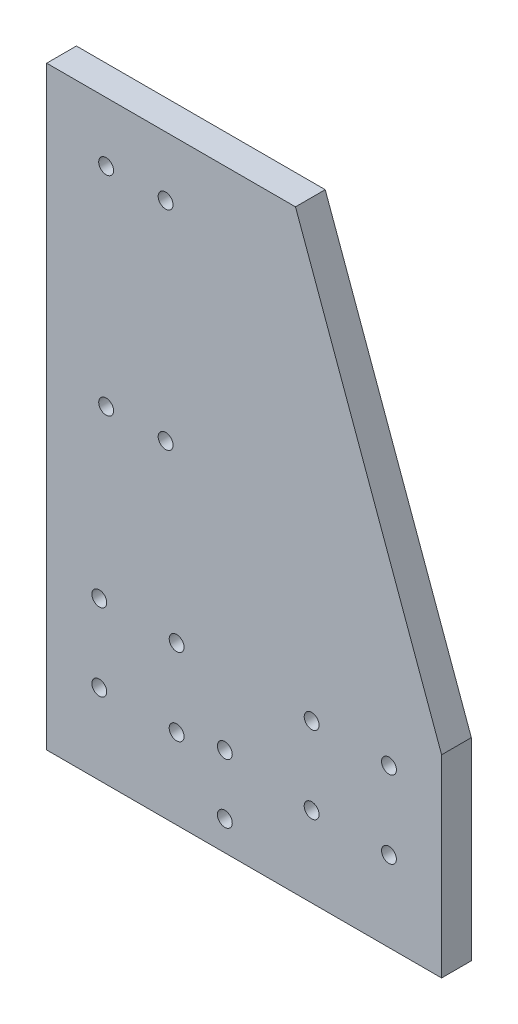
SolidWorks part; units mm, degrees
ref_plane "Front Plane" through (0, 0, 0) normal (0, 0, 1) x (1, 0, 0)
ref_plane "Top Plane" through (0, 0, 0) normal (0, 1, 0) x (1, 0, 0)
ref_plane "Right Plane" through (0, 0, 0) normal (1, 0, 0) x (0, 0, -1)
sketch "Sketch1" plane through (0, 0, 0) normal (0, 0, 1) x (1, 0, 0)
  line L0 (66.4, -5.8678) -> (66.4, 56.1407) construction
  line L5 (0, 0) -> (132.8, 0)
  line L6 (0, 0) -> (0, 200)
  line L7 (0, 200) -> (83.664, 200)
  line L8 (132.8, 0) -> (132.8, 65)
  line L9 (71.4, 57.9012) -> (71.4, -9.8319) construction
  line L23 (102.1, 57.9012) -> (102.1, -7.5742) construction
  line L24 (83.9369, 40) -> (119.8285, 40) construction
  line L25 (52.3456, 19.92) -> (67.8875, 19.92) construction
  line L26 (64.535, 29.92) -> (62.2225, 33.9254)
  line L27 (62.2225, 33.9254) -> (57.5975, 33.9254)
  line L28 (57.5975, 33.9254) -> (55.285, 29.92)
  line L29 (55.285, 29.92) -> (57.5975, 25.9146)
  line L30 (57.5975, 25.9146) -> (62.2225, 25.9146)
  line L31 (62.2225, 25.9146) -> (64.535, 29.92)
  line L32 (62.2225, 13.9254) -> (64.535, 9.92)
  line L33 (57.5975, 13.9254) -> (62.2225, 13.9254)
  line L34 (55.285, 9.92) -> (57.5975, 13.9254)
  line L35 (57.5975, 5.9146) -> (55.285, 9.92)
  line L36 (62.2225, 5.9146) -> (57.5975, 5.9146)
  line L37 (64.535, 9.92) -> (62.2225, 5.9146)
  line L38 (132.8, 65) -> (83.664, 200)
  circle A12 centre (115.1, 27) radius 2.5
  circle A13 centre (89.1, 27) radius 2.5
  circle A14 centre (115.1, 53) radius 2.5
  circle A15 centre (89.1, 53) radius 2.5
  circle A16 centre (17.7, 53) radius 2.5
  circle A17 centre (17.7, 27) radius 2.5
  circle A18 centre (43.7, 27) radius 2.5
  circle A19 centre (43.7, 53) radius 2.5
  circle A20 centre (59.91, 29.92) radius 4.0054 construction
  circle A21 centre (59.91, 29.92) radius 2.5
  circle A23 centre (59.91, 9.92) radius 2.5
  dimension "D4" = 5
  dimension "D13" = 5
  dimension "D1" = 200
  dimension "D2" = 132.8
  dimension "D3" = 26
  dimension "D5" = 61.4
  dimension "D6" = 30.7
  dimension "D7" = 27
  dimension "D8" = 13
  dimension "D9" = 29.92
  dimension "D10" = 10
  dimension "D11" = 9.25
  dimension "D12" = 11.49
  dimension "D14" = 65
  dimension "D15" = 20
  dimension "D16" = 9.92
extrude "Boss-Extrude1" add sketch "Sketch1" along normal blind 10 contours L8 L38 L7 L6 L5 A19 A17 A16 A14 A13 A12 L32 L37 L36 L35 L34 L33 L31 L30 L29 L28 L27 L26 A15 A18 | L30 L31 L26 L27 L28 L29 A21 | L37 L32 L33 L34 L35 L36 region at (59.2103, 92.8578, 0) region at (63.2728, 27.9785, 0) region at (63.2728, 11.8615, 0)
extrude "Cut-Extrude1" cut sketch "Sketch1<3>" along normal blind 5 contours L30 L31 L26 L27 L28 L29 A21 | L37 L32 L33 L34 L35 L36 region at (63.2728, 27.9785, 0) region at (63.2728, 11.8615, 0)
sketch "Sketch1<3>" plane through (0, 0, 0) normal (0, 0, 1) x (1, 0, 0) same geometry as "Sketch1"
sketch "Sketch2" plane through (0, 0, 0) normal (0, 0, -1) x (-1, 0, 0)
  line L9 (0, 200) -> (-83.664, 200) construction
  line L10 (0, 0) -> (0, 200) construction
  circle A0 centre (-40, 180) radius 2.5
  circle A1 centre (-20, 180) radius 2.5
  circle A2 centre (-40, 110) radius 2.5
  circle A3 centre (-20, 110) radius 2.5
  dimension "D2" = 5
  dimension "D1" = 20
  dimension "D4" = 20
  dimension "D5" = 2
  dimension "D6" = 70
  dimension "D3" = 20
extrude "Cut-Extrude2" cut sketch "Sketch2" against normal through all
